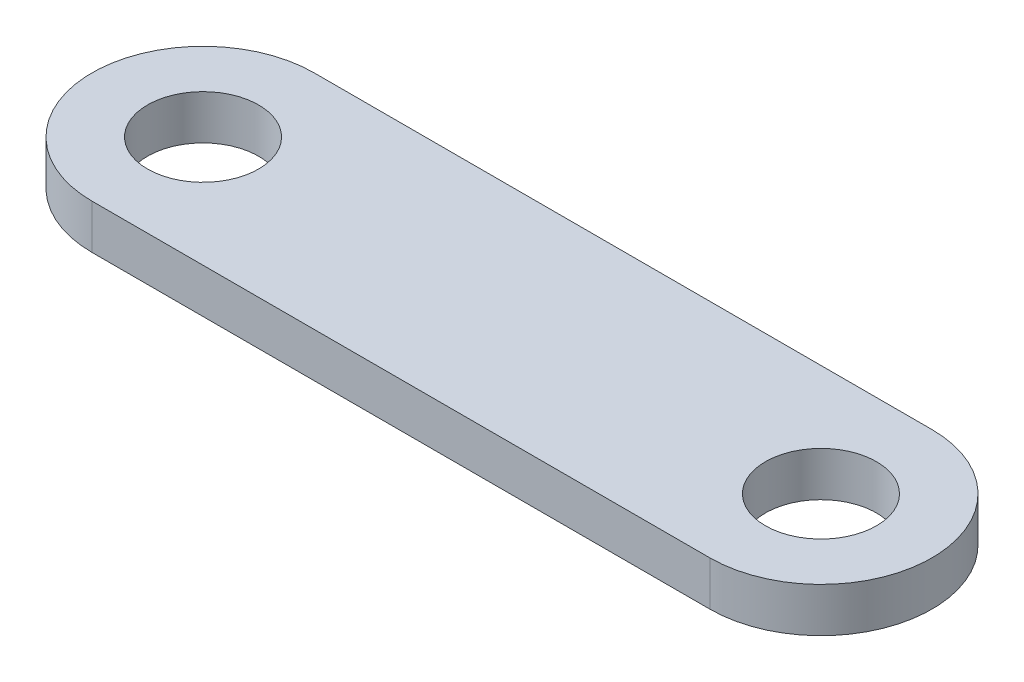
SolidWorks part; units mm, degrees
ref_plane "Front Plane" through (0, 0, 0) normal (0, 0, 1) x (1, 0, 0)
ref_plane "Top Plane" through (0, 0, 0) normal (0, 1, 0) x (1, 0, 0)
ref_plane "Right Plane" through (0, 0, 0) normal (1, 0, 0) x (0, 0, -1)
sketch "Sketch1" plane through (0, 0, 0) normal (0, 1, 0) x (1, 0, 0)
  line L0 (-17.6604, 0) -> (17.6604, 0) construction
  line L1 (-17.6604, 0) -> (17.6604, 0) construction
  line L2 (-17.6604, 6.35) -> (17.6604, 6.35)
  line L3 (-17.6604, -6.35) -> (17.6604, -6.35)
  arc A0 (-17.6604, 6.35) -> (-17.6604, -6.35) centre (-17.6604, 0) ccw
  arc A1 (17.6604, -6.35) -> (17.6604, 6.35) centre (17.6604, 0) ccw
  circle A2 centre (-17.6604, 0) radius 3.175
  circle A3 centre (17.6604, 0) radius 3.175
  point P3 (0, 0)
  dimension "D2" = 6.35
  dimension "D3" = 6.35
  dimension "D4" = 6.35
  dimension "D1" = 35.3207
extrude "Boss-Extrude1" add sketch "Sketch1" along normal blind 2.54
